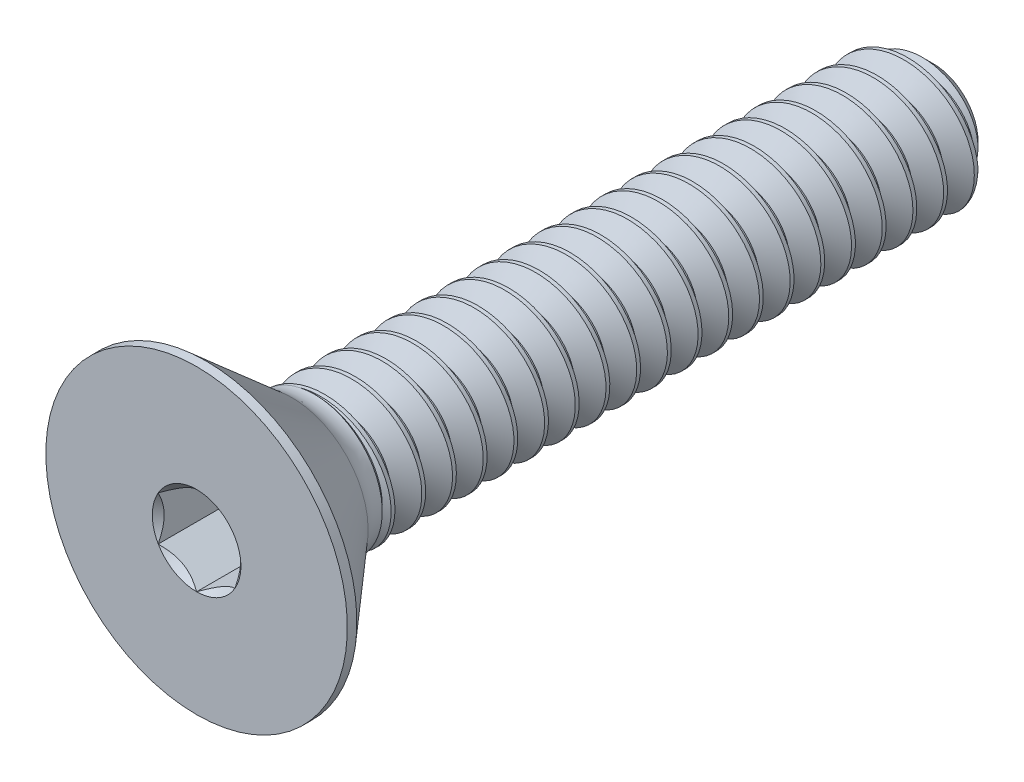
SolidWorks part; units mm, degrees
ref_plane "Front" through (0, 0, 0) normal (0, 0, 1) x (1, 0, 0)
ref_plane "Top" through (0, 0, 0) normal (0, 1, 0) x (1, 0, 0)
ref_plane "Right" through (0, 0, 0) normal (1, 0, 0) x (0, 0, -1)
sketch "Sketch1" plane through (0, 0, 0) normal (1, 0, 0) x (0, 0, -1)
  line L0 (0, 3.8989) -> (0.2464, 3.8989) construction
  line L1 (0.2464, 3.8989) -> (2.4638, 1.9713) construction
  line L2 (0, 1.7526) -> (19.05, 1.7526)
  line L3 (19.05, 1.7526) -> (19.05, 0)
  line L4 (19.05, 0) -> (0, 0)
  line L5 (0, 0) -> (0, 3.8989) construction
  line L6 (0, 3.8989) -> (0, -3.8989) construction
  line L7 (19.05, 1.7526) -> (19.05, -1.7526) construction
  line L8 (0, -3.8989) -> (0.2464, -3.8989) construction
  line L9 (0.2464, -3.8989) -> (2.4638, -1.9713) construction
  line L11 (0, 1.7526) -> (0, 0)
  line L12 (3.0488, 1.7526) -> (3.0488, 0) construction
  arc A1 (2.4638, 1.9713) -> (3.0488, 1.7526) centre (3.0488, 2.6443) ccw construction
  dimension "D1" = 0.2464
revolve "Revolve1" add sketch "Sketch1" angle 360 mid plane about L4
sketch "Sketch3" plane through (0, 0, -19.05) normal (0, 0, -1) x (-1, 0, 0)
  circle A0 centre (0, 0) radius 1.7526
curve "Helix/Spiral1" pitch 0.7937 height 19.05 radius 1.7526 centre (0, 0, -19.05) axis (0, 0, 1) start towards (0, 1, 0)
sketch "Sketch2" plane through (0, 0, 0) normal (1, 0, 0) x (0, 0, -1)
  line L0 (19.05, 1.7526) -> (19.7445, 1.7526)
  line L1 (19.7445, 1.7526) -> (19.4469, 1.237)
  line L2 (19.4469, 1.237) -> (19.3477, 1.237)
  line L3 (19.3477, 1.237) -> (19.05, 1.7526)
  line L4 (19.1988, 1.4948) -> (19.5957, 1.4948) construction
  dimension "D1" = 60
  dimension "D2" = 0.0992
  dimension "D3" = 0.3969
chamfer "Chamfer1" distance 0.5953 angle 45 1 edges at (0, 1.7526, -19.05)
sweep "Cut-Sweep1" cut profiles "Sketch2" path "Helix/Spiral1" align with end faces yes
sketch "Sketch7" plane through (0, 0, 0) normal (1, 0, 0) x (0, 0, -1)
  line L0 (0, 3.8989) -> (0.2464, 3.8989) construction
  line L1 (0.2464, 3.8989) -> (2.4638, 1.9713) construction
  line L2 (0, 3.8989) -> (0.2464, 3.8989)
  line L3 (0.2464, 3.8989) -> (2.4638, 1.9713)
  line L4 (3.0488, 1.7526) -> (3.0488, 0) construction
  line L5 (3.0488, 1.7526) -> (3.0488, 0)
  line L7 (0, 0) -> (0, 3.8989) construction
  line L8 (0, 0) -> (0, 3.8989)
  line L9 (0, 0) -> (3.0488, 0)
  line L10 (4.2888, 0) -> (-4.2888, 0) construction
  arc A0 (2.4638, 1.9713) -> (3.0488, 1.7526) centre (3.0488, 2.6443) ccw construction
  arc A1 (2.4638, 1.9713) -> (3.0488, 1.7526) centre (3.0488, 2.6443) ccw
revolve "Revolve2" add sketch "Sketch7" angle 360 mid plane about L9
ref_plane "Plane1" through (0, 0, -3.0488) normal (0, 0, 1) x (1, 0, 0)
sketch "Sketch8" plane through (0, 0, -3.0488) normal (0, 0, 1) x (1, 0, 0)
  circle A0 centre (0, 0) radius 1.7526
extrude "Boss-Extrude1" add sketch "Sketch8" against normal through all draft 45
sketch "Sketch5" plane through (0, 0, 0) normal (0, 0, 1) x (1, 0, 0)
  line L1 (0.9922, -0.5728) -> (0.9922, 0.5728)
  line L2 (0.9922, 0.5728) -> (0, 1.1457)
  line L3 (0, 1.1457) -> (-0.9922, 0.5728)
  line L4 (-0.9922, 0.5728) -> (-0.9922, -0.5728)
  line L5 (-0.9922, -0.5728) -> (0, -1.1457)
  line L6 (0, -1.1457) -> (0.9922, -0.5728)
  circle A0 centre (0, 0) radius 0.9922 construction
  dimension "Hex" = 1.9844
extrude "Cut-Extrude2" cut sketch "Sketch5" against normal blind 1.7247
sketch "Sketch6" plane through (0, 0, 0) normal (0, 0, 1) x (1, 0, 0)
  circle A0 centre (0, 0) radius 1.1457
extrude "Cut-Extrude3" cut sketch "Sketch6" against normal blind 1.7247 draft 45
sketch "Sketch9" [suppressed] plane through (0, 0, -3.0488) normal (0, 0, 1) x (1, 0, 0)
  circle A1 centre (0, 0) radius 1.7526
  circle A2 centre (0, 0) radius 1.7526
  point P0 (0, 1.7526)
  dimension "D1" = 0
extrude "Boss-Extrude2" [suppressed] add sketch "Sketch9" against normal offset from surface (28.7012 mm away) 22.225
sketch "Sketch10" plane through (0, 0, 0) normal (1, 0, 0) x (0, 0, -1)
  line L0 (19.05, 1.7526) -> (19.05, -1.7526) construction
  point P0 (17.8594, -1.7526)
  dimension "D1" = 1.1906
equation "\"D3@Helix/Spiral1\" = \"Lg@Sketch1\""
equation "\"D2@Sketch2\" = \"D4@Helix/Spiral1\" * .125"
equation "\"D3@Sketch2\" = \"D4@Helix/Spiral1\" * .5"
equation "\"D1@Chamfer1\" = \"D4@Helix/Spiral1\" * .75"
equation "\"D1@Cut-Extrude2\" = \"Head Ht@Sketch1\" * .7"
equation "\"D1@Sketch1\" = \"Head Ht@Sketch1\" * .1"
equation "\"D1@Sketch10\" = \"D4@Helix/Spiral1\" * 1.5"
equation "\"D1@Cut-Extrude3\" = \"D1@Cut-Extrude2\""
